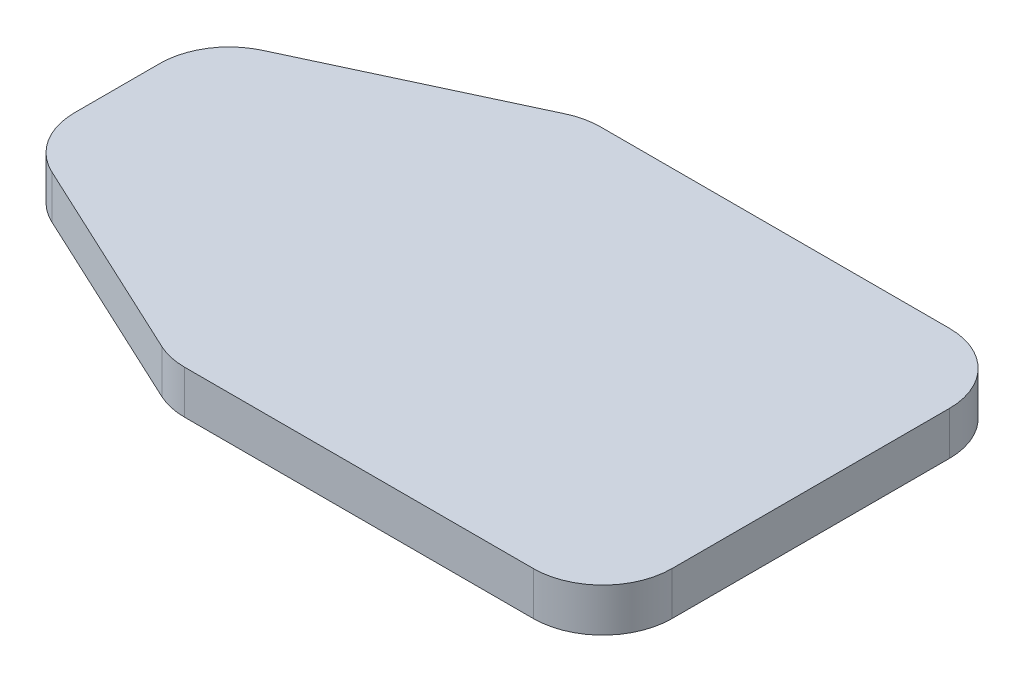
SolidWorks part; units mm, degrees
ref_plane "Front Plane" through (0, 0, 0) normal (0, 0, 1) x (1, 0, 0)
ref_plane "Top Plane" through (0, 0, 0) normal (0, 1, 0) x (1, 0, 0)
ref_plane "Right Plane" through (0, 0, 0) normal (1, 0, 0) x (0, 0, -1)
sketch "Sketch1" plane through (0, 0, 0) normal (0, 1, 0) x (1, 0, 0)
  line L0 (-25.4, 6.35) -> (-6.35, 15.24)
  line L1 (-25.4, 15.24) -> (25.4, 15.24)
  line L2 (-25.4, 15.24) -> (-25.4, -15.24)
  line L3 (-25.4, -15.24) -> (25.4, -15.24)
  line L4 (25.4, 15.24) -> (25.4, -15.24)
  line L5 (-25.4, -6.35) -> (-6.35, -15.24)
  point P4 (0, 15.24)
  point P5 (-25.4, 0)
  dimension "D1" = 30.48
  dimension "D2" = 50.8
  dimension "D3" = 19.05
  dimension "D4" = 8.89
extrude "Boss-Extrude1" add sketch "Sketch1" along normal blind 3.175 contours L2 L5 L3 L4 L1 L0 region at (2.3395, 0, 0)
fillet "Fillet2" radius 5.08 6 edges at (25.4, 1.5875, 15.24) (25.4, 1.5875, -15.24) (-6.35, 1.5875, -15.24) (-25.4, 1.5875, -6.35) (-25.4, 1.5875, 6.35) (-6.35, 1.5875, 15.24)
move or copy body "Body-Move/Copy1" [suppressed] bodies to move or copy 101 parameters "D1"=0, "D2"=0, "D3"=0
